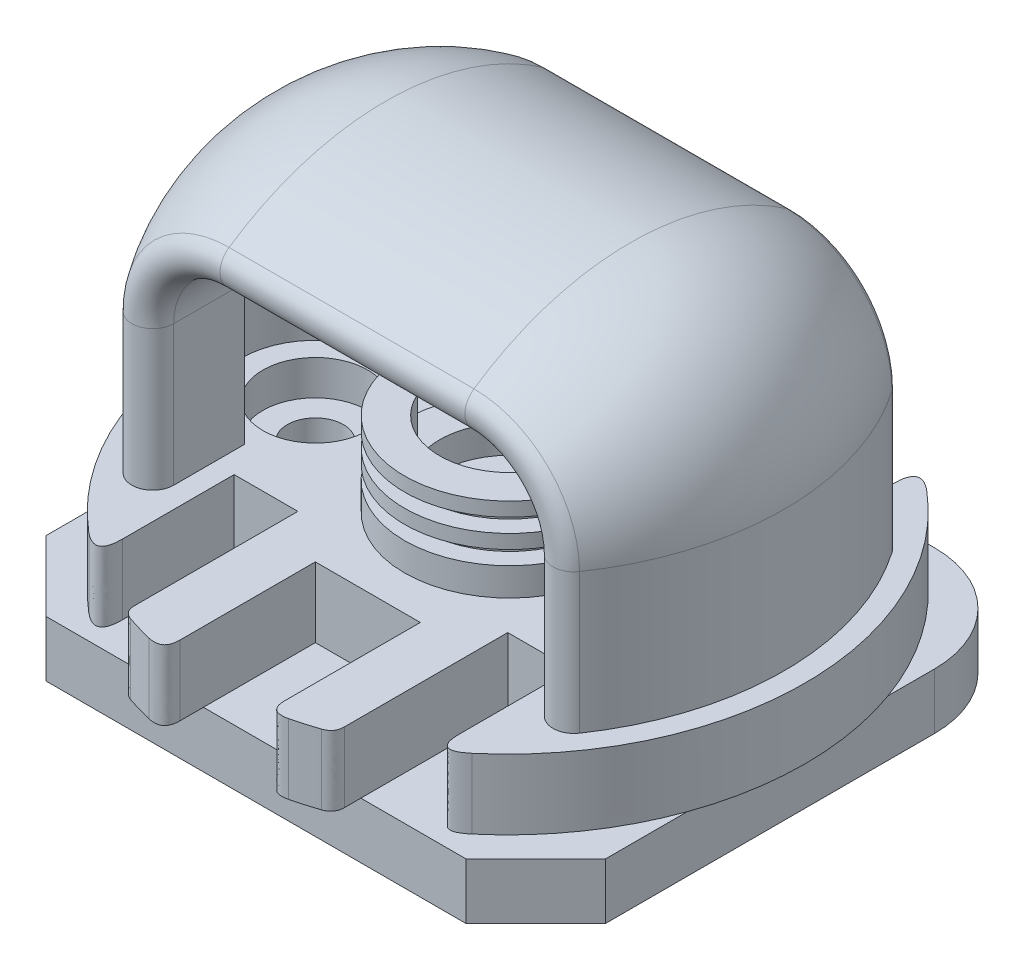
SolidWorks part; units mm, degrees
material "AISI 1020"
ref_plane "Front Plane" through (0, 0, 0) normal (0, 0, 1) x (1, 0, 0)
ref_plane "Top Plane" through (0, 0, 0) normal (0, 1, 0) x (1, 0, 0)
ref_plane "Right Plane" through (0, 0, 0) normal (1, 0, 0) x (0, 0, -1)
sketch "Sketch2" plane through (0, 0, 0) normal (0, 1, 0) x (1, 0, 0)
  line L1 (0, 0) -> (80, 0)
  line L2 (0, 0) -> (0, 72)
  line L3 (0, 72) -> (80, 72)
  line L4 (80, 0) -> (80, 72)
  dimension "A" = 80
  dimension "B" = 72
extrude "Boss-Extrude1" add sketch "Sketch2" along normal blind 8
sketch "Sketch3" plane through (0, 8, 0) normal (0, 1, 0) x (1, 0, 0)
  line L0 (0, 36) -> (80, 36) construction
  line L1 (0, 72) -> (0, 0) construction
  line L2 (80, 0) -> (80, 72) construction
  line L3 (40, 16) -> (40, 56) construction
  line L6 (32.5, 65.0474) -> (32.5, 56)
  line L7 (32.5, 56) -> (47.5, 56)
  line L8 (47.5, 56) -> (47.5, 65.0474)
  line L9 (25, 61.9808) -> (25, 51)
  line L10 (25, 51) -> (15.8909, 51)
  line L11 (15.8909, 51) -> (15.8909, 71)
  line L12 (55, 61.9808) -> (55, 51)
  line L13 (55, 51) -> (64.1091, 51)
  line L14 (64.1091, 51) -> (64.1091, 71)
  line L15 (25, -3.7649) -> (25, 21)
  line L16 (15.8909, 21) -> (15.8909, 1)
  line L17 (25, 21) -> (15.8909, 21)
  line L18 (32.5, -5.833) -> (32.5, 16)
  line L19 (32.5, 16) -> (47.5, 16)
  line L20 (47.5, 16) -> (47.5, -5.833)
  line L21 (64.1091, 21) -> (64.1091, 1)
  line L22 (55, 21) -> (64.1091, 21)
  line L23 (55, -3.7649) -> (55, 21)
  arc A0 (15.8909, 71) -> (15.8909, 1) centre (40, 36) ccw
  arc A3 (64.1091, 1) -> (64.1091, 71) centre (40, 36) ccw
  arc A4 (47.5, -5.833) -> (55, -3.7649) centre (40, 36) ccw
  arc A5 (25, -3.7649) -> (32.5, -5.833) centre (40, 36) ccw
  arc A6 (25, 61.9808) -> (32.5, 65.0474) centre (40, 36) cw
  arc A7 (47.5, 65.0474) -> (55, 61.9808) centre (40, 36) cw
  point P19 (40, 36)
  dimension "D1" = 15
  dimension "DIA" = 85
  dimension "D4" = 30
  dimension "D2" = 15
  dimension "D3" = 20
  dimension "E1" = 15
  dimension "D5" = 20
extrude "Boss-Extrude2" add sketch "Sketch3" along normal blind 10 contours A4 L23 L22 L21 A3 L14 L13 L12 A7 L8 L7 L6 A6 L9 L10 L11 A0 L16 L17 L15 A5 L18 L19 L20
chamfer "Chamfer1" distance 10 angle 45 2 edges at (0, 4, 0) (80, 4, 0)
fillet "Fillet1" radius 15 2 edges at (80, 4, -72) (0, 4, -72)
sketch "Sketch4" plane through (0, 18, 0) normal (0, 1, 0) x (1, 0, 0)
  line L0 (-2.5, 36) -> (82.5, 36) construction
  line L2 (40, 56) -> (40, 16) construction
  line L3 (32.5, 16) -> (47.5, 16) construction
  line L4 (32.5, 56) -> (47.5, 56) construction
  circle A0 centre (40.2538, 36) radius 15
  arc A1 (15.8909, 71) -> (15.8909, 1) centre (40, 36) ccw construction
  arc A2 (64.1091, 1) -> (64.1091, 71) centre (40, 36) ccw construction
  circle A3 centre (40.2538, 36) radius 10
  dimension "DiaUP" = 30
  dimension "T1" = 5
extrude "Boss-Extrude3" add sketch "Sketch4" along normal blind 12
sketch "Sketch5" plane through (0, 0, 0) normal (1, 0, 0) x (0, 0, -1)
  line L0 (36, 30) -> (36, 8) construction
  line L1 (51, 30) -> (21, 30) construction
  line L2 (21.6386, 8) -> (50.3614, 8) construction
  line L3 (46, 30) -> (26, 30) construction
  line L4 (32, 30) -> (40, 30)
  line L5 (32, 30) -> (32, 22)
  line L6 (32, 22) -> (40, 22)
  line L7 (40, 30) -> (40, 22)
  dimension "D1" = 8
  dimension "D2" = 8
extrude "Cut-Extrude1" cut sketch "Sketch5" along normal through all contours L7 L6 L5 L4
hole_wizard "CBORE for M10 Hex Head Bolt1" positions "Sketch6" profile "Sketch7" counterbore size "M10" standard "ANSI Metric" end condition through all
sketch "Sketch6" plane through (0, 18, 0) normal (0, 1, 0) x (1, 0, 0)
  line L0 (82.5, 36) -> (-2.5, 36) construction
  line L2 (40, 16) -> (40, 56) construction
  line L3 (32.5, 16) -> (47.5, 16) construction
  line L4 (32.5, 56) -> (47.5, 56) construction
  arc A0 (64.1091, 1) -> (64.1091, 71) centre (40, 36) ccw construction
  arc A1 (15.8909, 71) -> (15.8909, 1) centre (40, 36) ccw construction
  point P0 (67.5, 36)
  point P2 (12.5, 36)
  dimension "HoleD" = 55
sketch "Sketch7" plane through (67.5, 18, -36) normal (1, 0, 0) x (0, 0, 1)
  line L0 (0, 0) -> (0, 18)
  line L1 (0, 18) -> (4, 18)
  line L3 (4, 18) -> (4, 5)
  line L4 (4, 5) -> (7.5, 5)
  line L5 (7.5, 5) -> (7.5, 0)
  line L7 (7.5, 0) -> (0, 0)
  line L11 (0, -6.35) -> (0, 107.95) construction
  dimension "Thru Hole Dia." = 8
  dimension "Thru Hole Depth" = 18
  dimension "C'Bore Dia." = 15
  dimension "C'Bore Depth" = 5
sketch "Sketch8" plane through (0, 0, -72) normal (0, 0, -1) x (-1, 0, 0)
  line L0 (-65, 0) -> (-15, 0) construction
  line L1 (-55, 0) -> (-25, 0)
  line L2 (-55, 0) -> (-55, 4)
  line L3 (-55, 4) -> (-25, 4)
  line L4 (-25, 0) -> (-25, 4)
  line L5 (-25, 18) -> (-25, 8) construction
  line L7 (-55, 18) -> (-55, 8) construction
  dimension "D1" = 4
extrude "Cut-Extrude2" [suppressed] cut sketch "Sketch8" against normal through all
fillet "Fillet2" radius 2 12 edges at (64.1091, 13, -71) (15.8909, 13, -71) (15.8909, 13, -1) (64.1091, 13, -1) (55, 13, 3.7649) (47.5, 13, 5.833) (32.5, 13, 5.833) (25, 13, 3.7649) (55, 13, -61.9808) (47.5, 13, -65.0474) (32.5, 13, -65.0474) (25, 13, -61.9808) conic rho 0.5
sketch "Sketch9" plane through (0, 0, 0) normal (0, -1, 0) x (1, 0, 0)
  line L66 (77, -11.2426) -> (68.7574, -3)
  line L67 (77, -57) -> (77, -11.2426)
  line L68 (15, -69) -> (65, -69)
  line L69 (3, -11.2426) -> (3, -57)
  line L70 (11.2426, -3) -> (3, -11.2426)
  line L71 (68.7574, -3) -> (11.2426, -3)
  line L72 (77, -11.2426) -> (68.7574, -3)
  line L73 (77, -57) -> (77, -11.2426)
  line L74 (15, -69) -> (65, -69)
  line L75 (3, -11.2426) -> (3, -57)
  line L76 (11.2426, -3) -> (3, -11.2426)
  line L77 (68.7574, -3) -> (11.2426, -3)
  arc A35 (65, -69) -> (77, -57) centre (65, -57) ccw
  arc A36 (3, -57) -> (15, -69) centre (15, -57) ccw
  arc A37 (65, -69) -> (77, -57) centre (65, -57) ccw
  arc A38 (3, -57) -> (15, -69) centre (15, -57) ccw
  circle A45 centre (67.5, -36) radius 7
  circle A46 centre (67.5, -36) radius 7
  circle A48 centre (12.5, -36) radius 7
  circle A49 centre (12.5, -36) radius 7
  dimension "D1" = 3
  dimension "D2" = 3
  dimension "D3" = 3
extrude "Cut-Extrude3" cut sketch "Sketch9" against normal blind 5
sketch "Sketch10" plane through (0, 30, 0) normal (0, 1, 0) x (1, 0, 0)
  circle A0 centre (40.2538, 36) radius 12.5
  arc A2 (49.4189, 40) -> (31.0886, 40) centre (40.2538, 36) ccw construction
  circle A3 centre (40.2538, 36) radius 15
  line M2 (49.4189, 40) -> (54.7106, 40)
  arc M3 (54.7106, 40) -> (25.7969, 40) centre (40.2538, 36) ccw
  line M4 (25.7969, 40) -> (31.0886, 40)
  dimension "D1" = 25
sketch "Sketch11" plane through (0, 18, 0) normal (0, 1, 0) x (1, 0, 0)
  line L0 (67.1091, 25.5073) -> (67.1091, 15.3677)
  line L6 (67.1091, 56.6323) -> (67.1091, 46.4927)
  line L7 (64.1091, 21) -> (64.1091, 5.0393) construction
  arc A0 (67.1091, 15.3677) -> (72.5838, 13.6719) centre (70.1091, 15.3677) ccw
  arc A1 (72.5838, 58.3281) -> (67.1091, 56.6323) centre (70.1091, 56.6323) ccw
  arc A2 (65.4645, 5.8038) -> (65.4645, 66.1962) centre (40, 36) ccw
  arc A3 (72.5838, 13.6719) -> (72.5838, 58.3281) centre (40, 36) ccw
  circle A6 centre (67.5, 36) radius 10.5
  arc A7 (67.1091, 25.5073) -> (67.1091, 46.4927) centre (67.5, 36) ccw
  dimension "D3" = 3
  dimension "D4" = 3
  dimension "D2" = 3
  dimension "D1" = 3
ref_plane "Plane1" through (0, 0, -36) normal (0, 0, 1) x (1, 0, 0)
sketch "Sketch12" plane through (0, 0, -36) normal (0, 0, 1) x (1, 0, 0)
  line L0 (67.5, 18) -> (67.5, 38)
  line L1 (78, 18) -> (67.1091, 18) construction
  line L2 (12.5, 18) -> (12.5, 38)
  line L3 (20, 18) -> (5, 18) construction
  line L4 (22.5, 48) -> (57.5, 48)
  arc A0 (22.5, 48) -> (12.5, 38) centre (22.5, 38) ccw
  arc A1 (67.5, 38) -> (57.5, 48) centre (57.5, 38) ccw
  point P11 (12.5, 48)
  point P14 (67.5, 48)
  dimension "D3" = 10
  dimension "D1" = 30
  dimension "D2" = 30
extrude "Cut-Extrude4" cut sketch "Sketch10" against normal blind 2 from offset 2 contours A3 A0 M4 M2 | A0 M2 M3 M4 region at (52.9388, 30, -38.0844) region at (40.2538, 30, -48.8094) offset against normal yes
pattern_linear "LPattern1" count 2 spacing 4 along (0, -1, 0) of "Cut-Extrude4"
sweep "Sweep2" add profiles "Sketch11" path "Sketch12"
